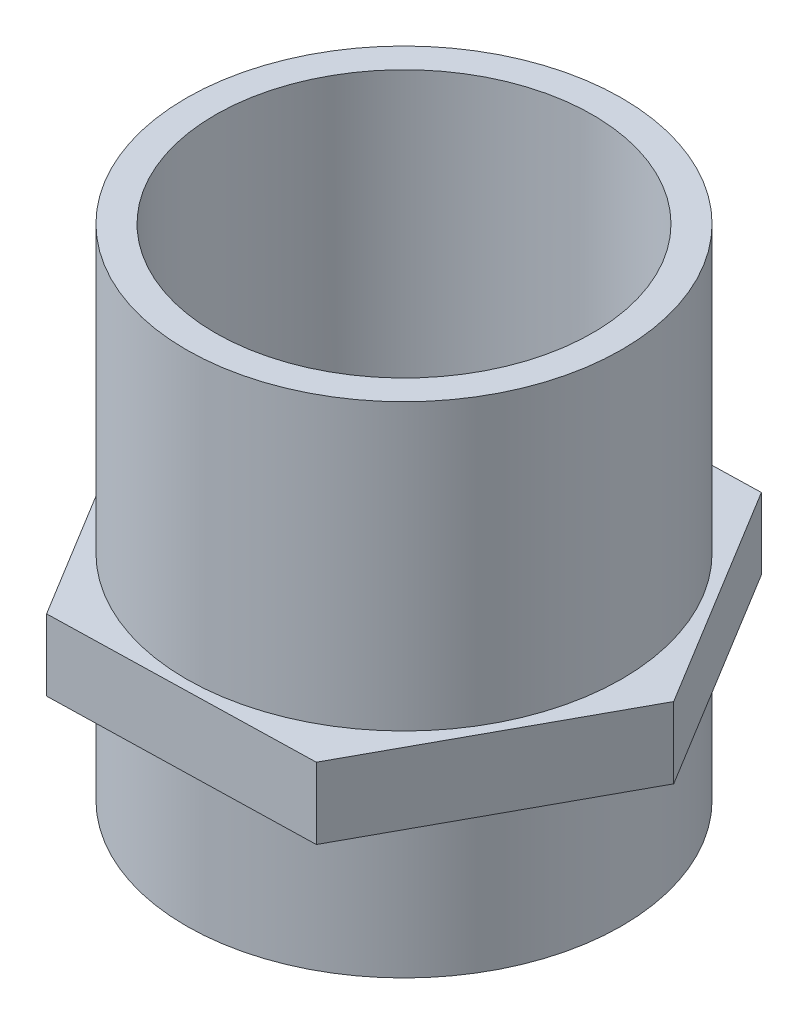
SolidWorks part; units mm, degrees
ref_plane "Front Plane" through (0, 0, 0) normal (0, 0, 1) x (1, 0, 0)
ref_plane "Top Plane" through (0, 0, 0) normal (0, 1, 0) x (1, 0, 0)
ref_plane "Right Plane" through (0, 0, 0) normal (1, 0, 0) x (0, 0, -1)
sketch "Sketch1" plane through (0, 0, 0) normal (0, 1, 0) x (1, 0, 0)
  line L1 (9.622, -15.7718) -> (18.4698, 0.447)
  line L2 (18.4698, 0.447) -> (8.8478, 16.2188)
  line L3 (8.8478, 16.2188) -> (-9.622, 15.7718)
  line L4 (-9.622, 15.7718) -> (-18.4698, -0.447)
  line L5 (-18.4698, -0.447) -> (-8.8478, -16.2188)
  line L6 (-8.8478, -16.2188) -> (9.622, -15.7718)
  circle A0 centre (0, 0) radius 15.279
  circle A1 centre (0, 0) radius 16 construction
  circle A2 centre (0, 0) radius 13.2418
  dimension "D1" = 32
extrude "Boss-Extrude1" add sketch "Sketch1" along normal blind 20 contours A2 | A0
extrude "Boss-Extrude2" add sketch "Sketch1<3>" against normal blind 15 contours A0 A2 region at (-14.8468, 0, 0)
sketch "Sketch1<3>" plane through (0, 0, 0) normal (0, 1, 0) x (1, 0, 0) same geometry as "Sketch1"
extrude "Boss-Extrude3" add sketch "Sketch1<4>" against normal blind 5 contours L5 L6 L1 L2 L3 L4 A0 region at (0.3752, 0, 15.5039)
sketch "Sketch1<4>" plane through (0, 0, 0) normal (0, 1, 0) x (1, 0, 0) same geometry as "Sketch1"
thread "Thread1" pitch 1.5875 method extrude profile "Thread Profile1" start angle 0, offset 0, length 10, pitch 1.5875, diameter 26.4835
ref_plane "Plane1" through (13.2418, -15, 0) normal (0, 0, 1) x (1, 0, 0)
sketch "Thread Profile1" plane through (13.2418, -15, 0) normal (0, 0, 1) x (1, 0, 0)
  line L0 (0, 0) -> (0, 1.5875) construction
  line L11 (0, 0) -> (0, 1.3891)
  line L12 (0, 1.3891) -> (-0.8593, 0.893)
  line L13 (-0.8593, 0.893) -> (-0.8593, 0.4961)
  line L15 (-0.8593, 0.4961) -> (0, 0)
  line L17 (-0.8593, 0.6945) -> (0, 0.6945) construction
  point P2 (0, 0)
  dimension "Pitch" = 1.5875
  dimension "Profile_Angle" = 60
  dimension "Profile_Land" = 0.3969
  dimension "Profile_Height" = 0.8593
